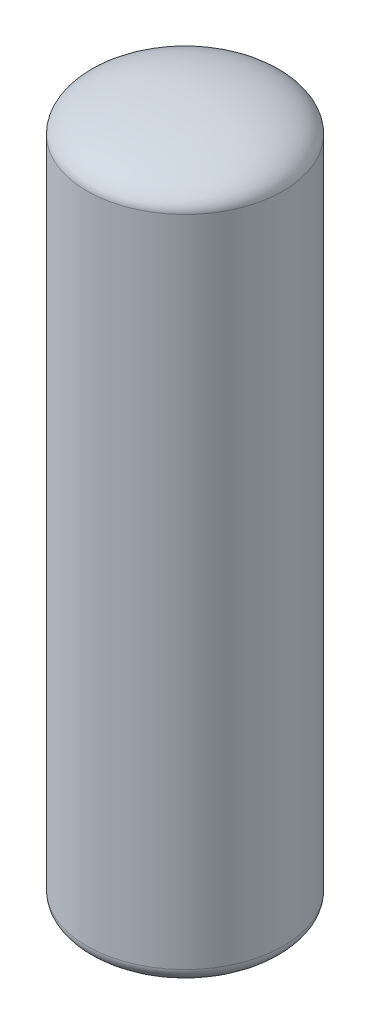
SolidWorks part; units mm, degrees
ref_plane "Plan de face" through (0, 0, 0) normal (0, 0, 1) x (1, 0, 0)
ref_plane "Plan de dessus" through (0, 0, 0) normal (0, 1, 0) x (1, 0, 0)
ref_plane "Plan de droite" through (0, 0, 0) normal (1, 0, 0) x (0, 0, -1)
sketch "Esquisse1" plane through (0, 0, 0) normal (0, 1, 0) x (1, 0, 0)
  circle A0 centre (0, 0) radius 3
  dimension "D1" = 6
extrude "Boss.-Extru.1" add sketch "Esquisse1" along normal blind 20
dome "Dôme1" faces to dome 1 distance 1 reverse direction no elliptical dome yes face at (0, 20, 3) parameters "D1"=1
dome "Dôme2" faces to dome 1 distance 1 reverse direction no elliptical dome yes face at (0, 0, 3) parameters "D1"=1
